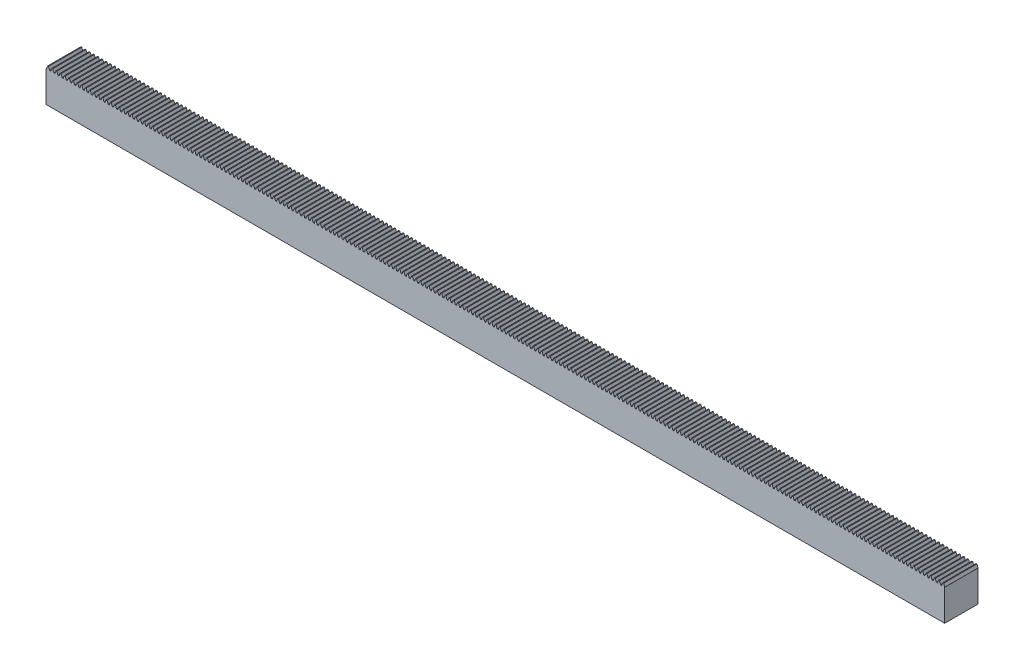
SolidWorks part; units mm, degrees
extrude "Blank" add sketch "BlankSke" against normal blind 50
sketch "BlankSke" plane through (0, 0, 0) normal (0, 0, 1) x (1, 0, 0)
  line L1 (0, 0) -> (1350, 0)
  line L2 (0, 0) -> (0, 51.4)
  line L3 (0, 51.4) -> (1350, 51.4)
  line L4 (1350, 0) -> (1350, 51.4)
  dimension "Length" = 1350
ref_plane "Plane1" through (0, 0, 0) normal (0, 0, 1) x (1, 0, 0)
ref_plane "Plane2" through (0, 0, 0) normal (0, 1, 0) x (1, 0, 0)
ref_plane "Plane3" through (0, 0, 0) normal (1, 0, 0) x (0, 0, -1)
sketch "HoldingSke" plane through (0, 0, 0) normal (0, 1, 0) x (1, 0, 0)
  line L0 (0, 0) -> (0.0696, 0.4951)
  line L1 (-15, 0) -> (100, 0) construction
  line L2 (0, 0) -> (-2.1039, 2.3779)
  line L3 (0, 0) -> (-11.863, 4.5341)
  line L4 (0, 0) -> (-6.9867, -5.0761)
  line L5 (0, 0) -> (-23.7986, -8.8762)
  line L6 (0, 0) -> (-10.5278, -7.1032)
  line L9 (-71.009, 38.7566) -> (1197.5761, 500.4838)
  line L10 (-76.2, 4.3779) -> (-26.8, 4.3779)
  line L11 (0, 0) -> (-50, 0)
  line L12 (-76.2, 101.6) -> (-76.133, 101.6)
  line L13 (24.9733, 27.94) -> (52.9518, 28.4284)
  line L14 (24.9733, 27.94) -> (24.9743, 27.94)
  line L15 (24.9733, 27.94) -> (100.4006, 29.5858)
  circle A0 centre (0, 0) radius 19.05
  circle A1 centre (0, 0) radius 24.7
  circle A2 centre (0, 0) radius 12.7
  dimension "Num_teeth" = 216
  dimension "Width" = 50
  dimension "Length" = 1350
  dimension "Pitch_height" = 49.4
sketch "TooCutSkeIll" plane through (0, 0, 0) normal (0, 0, 1) x (1, 0, 0)
  line L0 (-2.4806, 51.3474) -> (-0.9819, 47.2296)
  line L1 (-0.5111, 46.9) -> (0.5111, 46.9)
  line L2 (0.9819, 47.2296) -> (2.4806, 51.3474)
  line L3 (1350, 51.4) -> (0, 51.4) construction
  line L4 (0, 0) -> (0, 64.897) construction
  line L5 (-13.208, 49.4) -> (12.954, 49.4) construction
  line L6 (0, 0) -> (1350, 0) construction
  line L7 (1.7718, 49.4) -> (1.7718, 48.7463) construction
  line L8 (-1.7718, 49.4) -> (-1.7718, 48.7463) construction
  line L9 (2.5558, 51.4) -> (2.5558, 51.4254)
  line L10 (-2.5558, 51.4) -> (-2.5558, 51.4254)
  line L11 (-2.5558, 51.4254) -> (2.5558, 51.4254)
  arc A0 (0.5111, 46.9) -> (0.9819, 47.2296) centre (0.5111, 47.401) ccw
  arc A1 (-0.9819, 47.2296) -> (-0.5111, 46.9) centre (-0.5111, 47.401) ccw
  arc A2 (2.5558, 51.4) -> (2.4806, 51.3474) centre (2.5558, 51.32) ccw
  arc A3 (-2.4806, 51.3474) -> (-2.5558, 51.4) centre (-2.5558, 51.32) ccw
  dimension "Addendum_plus" = 2.0254
  dimension "Pitch_height" = 49.4
  dimension "Pressure_angle" = 20
  dimension "Gap_width" = 3.5436
  dimension "Dedendum" = 2.5
extrude "ToothCutIll" [suppressed] cut sketch "TooCutSkeIll" against normal through all
sketch "TooCutSkeSim" plane through (0, 0, 0) normal (0, 0, 1) x (1, 0, 0)
  line L0 (0.8619, 46.9) -> (-0.8619, 46.9)
  line L1 (2.509, 51.4254) -> (0.8619, 46.9)
  line L2 (0, 17.4625) -> (0, 53.467) construction
  line L3 (2.509, 51.4254) -> (-2.509, 51.4254)
  line L6 (-2.509, 51.4254) -> (-0.8619, 46.9)
  line L9 (-1.7718, 49.4) -> (1.7718, 49.4) construction
  line L10 (0, 0) -> (1350, 0) construction
  line L11 (1.7718, 49.4) -> (1.7718, 53.467) construction
  line L12 (-1.7718, 49.4) -> (-1.7718, 53.467) construction
  dimension "Addendum_plus" = 2.0254
  dimension "Pitch_height" = 49.4
  dimension "Pressure_angle" = 20
  dimension "Gap_width" = 3.5436
  dimension "Dedendum" = 2.5
extrude "ToothCutSim" cut sketch "TooCutSkeSim" against normal through all
pattern_linear "TeethCuts" count 216 spacing 6.2832 along (1, 0, 0) of "ToothCutIll", "ToothCutSim"
equation "' \"Module@HoldingSke\" = 6.35"
equation "' \"Num_teeth@HoldingSke\" = 12"
equation "' \"Ap@HoldingSke\" =  20"
equation "' \"Ap@HoldingSke\" = 20"
equation "' \"Width@HoldingSke\" = 0.25 * 25.4"
equation "' \"Show_teeth@HoldingSke\" = 500"
equation "' \"Backlash@HoldingSke\" = 0.009 * 25.4"
equation "' \"Addendum_fac@HoldingSke\" = 1.0"
equation "' \"Dedendum_fac@HoldingSke\" = 1.25"
equation "' \"Dedendum_add@HoldingSke\" = 0.00005 * 25.4"
equation "' \"Clearance_fac@HoldingSke\" = 0.25"
equation "' \"Pitch_height@HoldingSke\" = 1 * 25.4"
equation "' \"Length@HoldingSke\" = 4.71 * 25.4"
equation "\"Pitch@HoldingSke\" = 1 / \"Module@HoldingSke\""
equation "\"MPH@HoldingSke\" = \"Dedendum_fac@HoldingSke\" / \"Pitch@HoldingSke\" + 2 * \"Dedendum_add@HoldingSke\" + 0.002 * 25.4"
equation "\"MPH@HoldingSke\" = ((sgn( \"MPH@HoldingSke\" - \"Pitch_height@HoldingSke\")+1)*( \"MPH@HoldingSke\" - \"Pitch_height@HoldingSke\"))/2 + \"Pitch_height@HoldingSke\""
equation "\"Blank_height@BlankSke\" = \"Pitch_height@HoldingSke\" + \"Addendum_fac@HoldingSke\"  / \"Pitch@HoldingSke\" "
equation "\"Length@BlankSke\" =  \"Length@HoldingSke\""
equation "\"Face_width@Blank\" = \"Width@HoldingSke\""
equation "\"Pressure_angle@TooCutSkeIll\" = \"Ap@HoldingSke\""
equation "\"Addendum_plus@TooCutSkeIll\" =  \"Addendum_fac@HoldingSke\"  / \"Pitch@HoldingSke\" + 0.001 *25.4"
equation "\"Dedendum@TooCutSkeIll\" = \"Dedendum_fac@HoldingSke\"  / \"Pitch@HoldingSke\""
equation "\"Pitch_height@TooCutSkeIll\" =  \"MPH@HoldingSke\""
equation "\"Gap_width@TooCutSkeIll\" = 3.14159265 / 2 / \"Pitch@HoldingSke\" + 6 * \"Backlash@HoldingSke\""
equation "\"Pressure_angle@TooCutSkeSim\" = \"Ap@HoldingSke\""
equation "\"Addendum_plus@TooCutSkeSim\" =  \"Addendum_fac@HoldingSke\"  / \"Pitch@HoldingSke\" + 0.001 * 25.4"
equation "\"Dedendum@TooCutSkeSim\" = \"Dedendum_fac@HoldingSke\"  / \"Pitch@HoldingSke\""
equation "\"Pitch_height@TooCutSkeSim\" =  \"MPH@HoldingSke\""
equation "\"Gap_width@TooCutSkeSim\" = 3.14159265 / 2 / \"Pitch@HoldingSke\" + 6 * \"Backlash@HoldingSke\""
equation "\"Root_fillet@TooCutSkeIll\" = \"Clearance_fac@HoldingSke\" / \"Pitch@HoldingSke\" + \"Dedendum_add@HoldingSke\""
equation "\"Break_rad@TooCutSkeIll\" = 0.02 / \"Pitch@HoldingSke\" * 2"
equation "\"Linear_pitch@TeethCuts\" = 3.14159265 / \"Pitch@HoldingSke\""
equation "\"Num_teeth@HoldingSke\" = int( ( \"Length@HoldingSke\" + 0 ) / (3.14159265 / \"Pitch@HoldingSke\")) + 0.9999  + 1"
equation " \"Num_teeth@TeethCuts\" = int( \"Show_teeth@HoldingSke\" ) + 1"
equation " \"Num_teeth@TeethCuts\" = ((sgn( \"Num_teeth@TeethCuts\" - \"Num_teeth@HoldingSke\" )-1)*( \"Num_teeth@TeethCuts\" - \"Num_teeth@HoldingSke\" ))/-2+ \"Num_teeth@HoldingSke\""
equation " \"Num_teeth@TeethCuts\" = ((sgn( \"Num_teeth@TeethCuts\" - 2.0)+1)*( \"Num_teeth@TeethCuts\" - 2.0))/2 +2.0"
